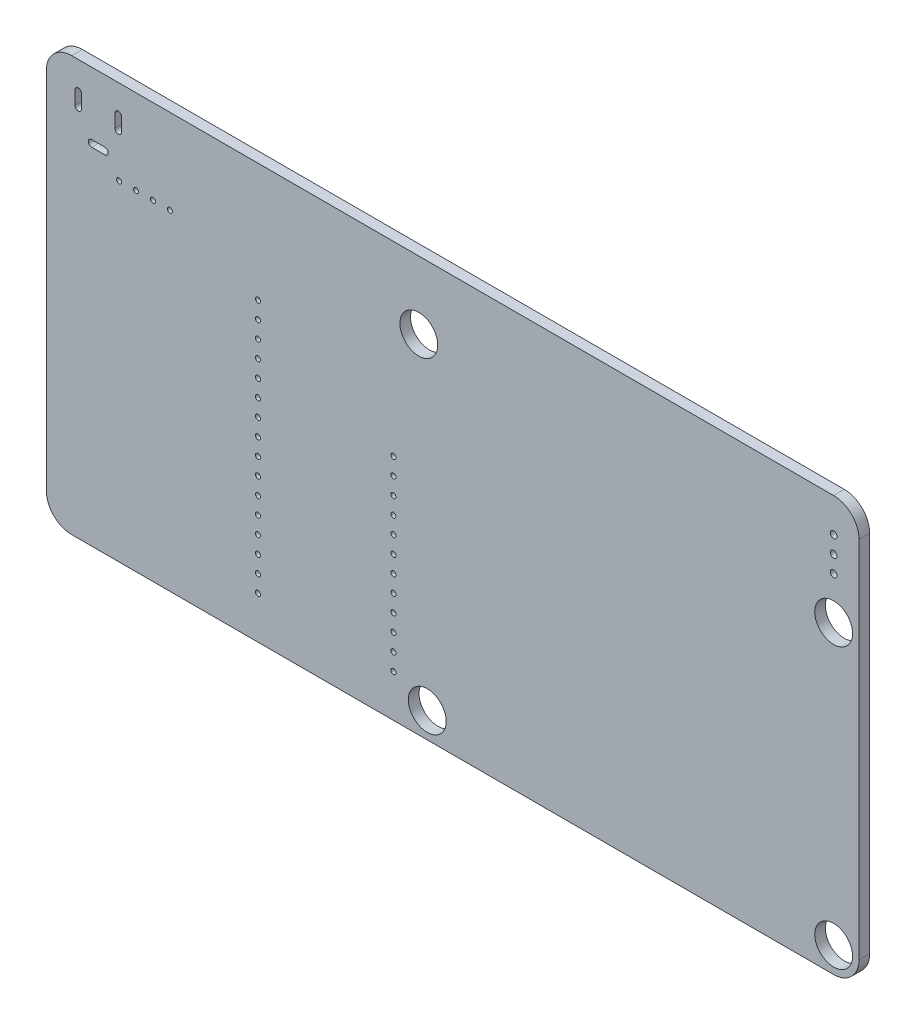
SolidWorks part; units mm, degrees
ref_plane "Plan de face" through (0, 0, 0) normal (0, 0, 1) x (1, 0, 0)
ref_plane "Plan de dessus" through (0, 0, 0) normal (0, 1, 0) x (1, 0, 0)
ref_plane "Plan de droite" through (0, 0, 0) normal (1, 0, 0) x (0, 0, -1)
ref_plane "Plan1" through (0, 0, 1.6) normal (0, 0, 1) x (1, 0, 0)
sketch "Esquisse1" plane through (0, 0, 1.6) normal (0, 0, 1) x (1, 0, 0)
  line L0 (32.925, -63.747) -> (30.925, -63.747)
  line L1 (30.925, -62.747) -> (32.925, -62.747)
  line L2 (29.425, -57.547) -> (29.425, -59.547)
  line L3 (28.425, -59.547) -> (28.425, -57.547)
  line L4 (35.425, -57.547) -> (35.425, -59.547)
  line L5 (34.425, -59.547) -> (34.425, -57.547)
  line L6 (146.05, -111.76) -> (146.05, -57.15)
  line L7 (142.24, -53.34) -> (27.94, -53.34)
  line L8 (24.13, -57.15) -> (24.13, -111.76)
  line L9 (27.94, -115.57) -> (142.24, -115.57)
  circle A0 centre (55.88, -109.22) radius 0.381
  circle A1 centre (55.88, -106.68) radius 0.381
  circle A2 centre (142.24, -111.76) radius 2.8398
  circle A3 centre (81.28, -111.76) radius 2.8398
  circle A4 centre (76.2, -106.68) radius 0.381
  circle A5 centre (76.2, -109.22) radius 0.381
  arc A6 (32.925, -62.747) -> (32.925, -63.747) centre (32.925, -63.247) cw
  arc A7 (30.925, -63.747) -> (30.925, -62.747) centre (30.925, -63.247) cw
  arc A8 (28.425, -57.547) -> (29.425, -57.547) centre (28.925, -57.547) cw
  arc A9 (29.425, -59.547) -> (28.425, -59.547) centre (28.925, -59.547) cw
  circle A10 centre (76.2, -104.14) radius 0.381
  circle A11 centre (55.88, -104.14) radius 0.381
  circle A12 centre (142.24, -58.42) radius 0.5
  circle A13 centre (142.24, -69.85) radius 2.8398
  circle A14 centre (142.24, -60.96) radius 0.5
  circle A15 centre (142.24, -63.5) radius 0.5
  circle A16 centre (80.01, -63.5) radius 2.8398
  circle A17 centre (55.88, -71.12) radius 0.381
  circle A18 centre (55.88, -73.66) radius 0.381
  circle A19 centre (55.88, -76.2) radius 0.381
  circle A20 centre (55.88, -78.74) radius 0.381
  circle A21 centre (42.672, -66.04) radius 0.381
  circle A22 centre (35.052, -66.04) radius 0.381
  circle A23 centre (37.592, -66.04) radius 0.381
  circle A24 centre (40.132, -66.04) radius 0.381
  arc A25 (34.425, -57.547) -> (35.425, -57.547) centre (34.925, -57.547) cw
  arc A26 (35.425, -59.547) -> (34.425, -59.547) centre (34.925, -59.547) cw
  circle A27 centre (76.2, -81.28) radius 0.381
  circle A28 centre (55.88, -81.28) radius 0.381
  circle A29 centre (76.2, -83.82) radius 0.381
  circle A30 centre (76.2, -86.36) radius 0.381
  circle A31 centre (76.2, -88.9) radius 0.381
  circle A32 centre (55.88, -86.36) radius 0.381
  circle A33 centre (55.88, -88.9) radius 0.381
  circle A34 centre (55.88, -83.82) radius 0.381
  circle A35 centre (76.2, -93.98) radius 0.381
  circle A36 centre (55.88, -93.98) radius 0.381
  circle A37 centre (76.2, -91.44) radius 0.381
  circle A38 centre (55.88, -91.44) radius 0.381
  circle A39 centre (76.2, -96.52) radius 0.381
  circle A40 centre (76.2, -99.06) radius 0.381
  circle A41 centre (76.2, -101.6) radius 0.381
  circle A42 centre (55.88, -101.6) radius 0.381
  circle A43 centre (55.88, -99.06) radius 0.381
  circle A44 centre (55.88, -96.52) radius 0.381
  arc A45 (146.05, -57.15) -> (142.24, -53.34) centre (142.24, -57.15) ccw
  arc A46 (27.94, -53.34) -> (24.13, -57.15) centre (27.94, -57.15) ccw
  arc A47 (24.13, -111.76) -> (27.94, -115.57) centre (27.94, -111.76) ccw
  arc A48 (142.24, -115.57) -> (146.05, -111.76) centre (142.24, -111.76) ccw
extrude "Boss.-Extru.1" add sketch "Esquisse1" against normal blind 1.6
sketch "Esquisse2" plane through (0, 0, 1.6) normal (0, 0, 1) x (1, 0, 0)
  line L0 (24.13, -53.34) -> (146.05, -115.57) construction
  line L1 (146.05, -115.57) -> (146.05, -53.34) construction
  line L2 (146.05, -53.34) -> (24.13, -115.57) construction
ref_plane "Plan2" through (-16.6115, -32.5449, 0) normal (0.4546, 0.8907, 0) x (0.8907, -0.4546, 0)
sketch "Esquisse3" plane through (-16.6115, -32.5449, 0) normal (0.4546, 0.8907, 0) x (0.8907, -0.4546, 0)
  line L0 (114.1834, -1.6) -> (114.1834, 54.0326) construction
  line L1 (45.7417, -1.6) -> (182.6251, -1.6) construction
ref_axis "Axe1" through (85.09, -84.455, 1.6) along (0, 0, -1)
